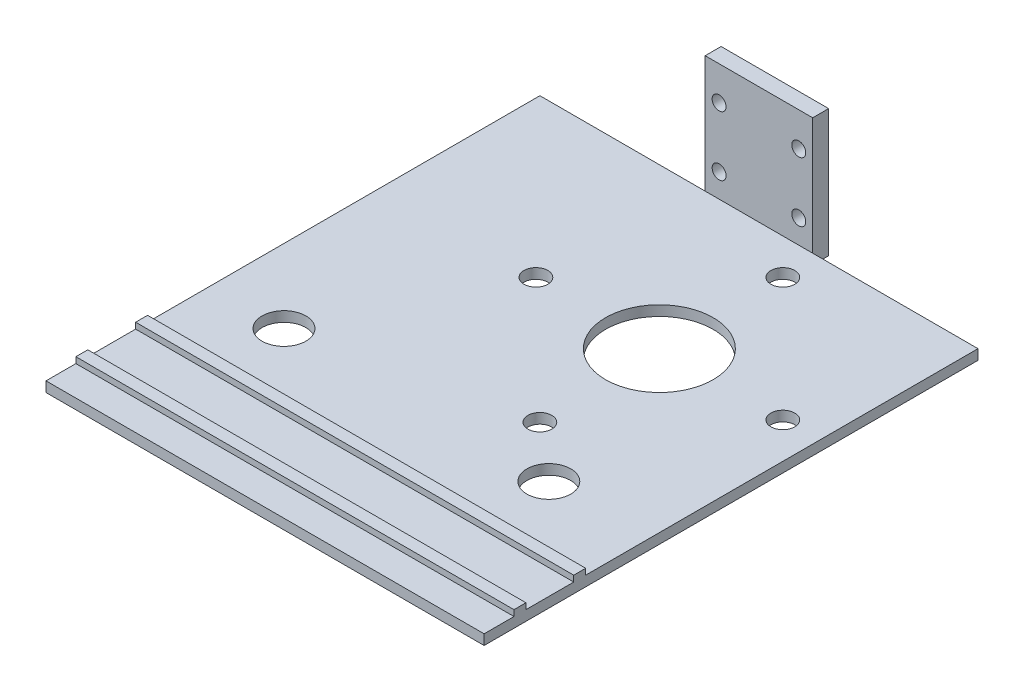
SolidWorks part; units mm, degrees
ref_plane "Piano frontale" through (0, 0, 0) normal (0, 0, 1) x (1, 0, 0)
ref_plane "Piano superiore" through (0, 0, 0) normal (0, 1, 0) x (1, 0, 0)
ref_plane "Piano destro" through (0, 0, 0) normal (1, 0, 0) x (0, 0, -1)
sketch "Schizzo1" plane through (0, 0, 0) normal (0, 0, 1) x (1, 0, 0)
  line L1 (0, 0) -> (27, 0)
  line L2 (0, 0) -> (0, -36)
  line L3 (0, -36) -> (27, -36)
  line L4 (27, 0) -> (27, -36)
  dimension "D1" = 27
  dimension "D2" = 36
extrude "Estrusione-Estrusione1" add sketch "Schizzo1" along normal blind 4
sketch "Schizzo10" plane through (0, 0, 4) normal (0, 0, 1) x (1, 0, 0)
  line L0 (27, 0) -> (0, 0) construction
  line L1 (3.5, -12.5) -> (23.5, -12.5) construction
  line L2 (3.5, -12.5) -> (3.5, -27.5) construction
  line L3 (3.5, -27.5) -> (23.5, -27.5) construction
  line L4 (23.5, -12.5) -> (23.5, -27.5) construction
  line L5 (27, -36) -> (27, 0) construction
  circle A0 centre (3.5, -12.5) radius 1.75
  circle A1 centre (23.5, -12.5) radius 1.75
  circle A2 centre (23.5, -27.5) radius 1.75
  circle A3 centre (3.5, -27.5) radius 1.75
  dimension "D5" = 3.5
  dimension "D1" = 12.5
  dimension "D2" = 15
  dimension "D3" = 20
  dimension "D4" = 3.5
extrude "Taglio-Estrusione5" cut sketch "Schizzo10" against normal blind 10
ref_plane "Piano1" through (13.5, 0, 0) normal (1, 0, 0) x (0, 0, -1)
sketch "Schizzo12" plane through (13.5, 0, 0) normal (1, 0, 0) x (0, 0, -1)
  line L1 (-4, -36) -> (-128, -36)
  line L2 (-4, -36) -> (-4, -33.4507)
  line L3 (-4, -33.4507) -> (-128, -33.4507)
  line L4 (-128, -36) -> (-128, -33.4507)
  dimension "D1" = 124
extrude "Estrusione-Estrusione2" add sketch "Schizzo12" along normal blind 55 and the other way blind 55
sketch "Schizzo14" plane through (-41.5, 0, 0) normal (-1, 0, 0) x (0, 0, 1)
  line L0 (4, -33.4507) -> (128, -33.4507) construction
  line L1 (102.5, -33.4507) -> (105.5, -33.4507)
  line L2 (102.5, -33.4507) -> (102.5, -31.9507)
  line L3 (102.5, -31.9507) -> (105.5, -31.9507)
  line L4 (105.5, -33.4507) -> (105.5, -31.9507)
  line L5 (128, -33.4507) -> (128, -36) construction
  line L6 (117.5, -33.4507) -> (120.5, -33.4507)
  line L7 (117.5, -33.4507) -> (117.5, -31.9507)
  line L8 (117.5, -31.9507) -> (120.5, -31.9507)
  line L9 (120.5, -33.4507) -> (120.5, -31.9507)
  dimension "D1" = 7.5
  dimension "D2" = 12
  dimension "D3" = 1.5
  dimension "D4" = 3
extrude "Estrusione-Estrusione3" add sketch "Schizzo14" against normal blind 110
sketch "Schizzo15" plane through (0, 0, 4) normal (0, 0, 1) x (1, 0, 0)
  line L0 (27, -33.4507) -> (27, 0) construction
  line L1 (0, 0) -> (27, 0)
  line L2 (0, 0) -> (0, -4)
  line L3 (0, -4) -> (27, -4)
  line L4 (27, 0) -> (27, -4)
  dimension "D1" = 4
extrude "Taglio-Estrusione6" cut sketch "Schizzo15" against normal through all
sketch "Schizzo16" plane through (0, -33.4507, 0) normal (0, 1, 0) x (1, 0, 0)
  line L0 (68.5, -44) -> (28.5, -44) construction
  line L1 (68.5, -4) -> (68.5, -102.5) construction
  line L2 (28.5, -4) -> (28.5, -44) construction
  line L3 (27, -4) -> (68.5, -4) construction
  circle A0 centre (28.5, -44) radius 13.5
  dimension "D3" = 27
  dimension "D1" = 40
  dimension "D2" = 40
extrude "Taglio-Estrusione7" cut sketch "Schizzo16" against normal blind 41
sketch "Schizzo17" plane through (0, -33.4507, 0) normal (0, 1, 0) x (1, 0, 0)
  line L0 (68.5, -4) -> (68.5, -102.5) construction
  line L1 (-41.5, -128) -> (68.5, -128) construction
  line L3 (27, -4) -> (68.5, -4) construction
  line L4 (-41.5, -4) -> (-41.5, -102.5) construction
  line L5 (-41.5, -4) -> (0, -4) construction
  circle A0 centre (28.5, -13) radius 3
  circle A1 centre (59.5, -44) radius 3
  circle A2 centre (29.5, -75) radius 3
  circle A3 centre (-2.5, -44) radius 3
  dimension "D3" = 6
  dimension "D1" = 39
  dimension "D2" = 53
  dimension "D4" = 9
  dimension "D5" = 40
  dimension "D6" = 9
  dimension "D7" = 40
  dimension "D8" = 39
  dimension "D9" = 40
extrude "Taglio-Estrusione8" cut sketch "Schizzo17" against normal through all
sketch "Schizzo18" plane through (0, -33.4507, 0) normal (0, 1, 0) x (1, 0, 0)
  line L0 (68.5, -4) -> (68.5, -102.5) construction
  line L1 (-41.5, -128) -> (68.5, -128) construction
  line L2 (43.5, -86.75) -> (-23, -86.75) construction
  line L3 (-41.5, -4) -> (-41.5, -102.5) construction
  circle A0 centre (43.5, -86.75) radius 5.5
  circle A1 centre (-23, -86.75) radius 5.5
  dimension "D1" = 11
  dimension "D3" = 41.25
  dimension "D2" = 25
  dimension "D4" = 18.5
extrude "Taglio-Estrusione9" cut sketch "Schizzo18" against normal blind 10
